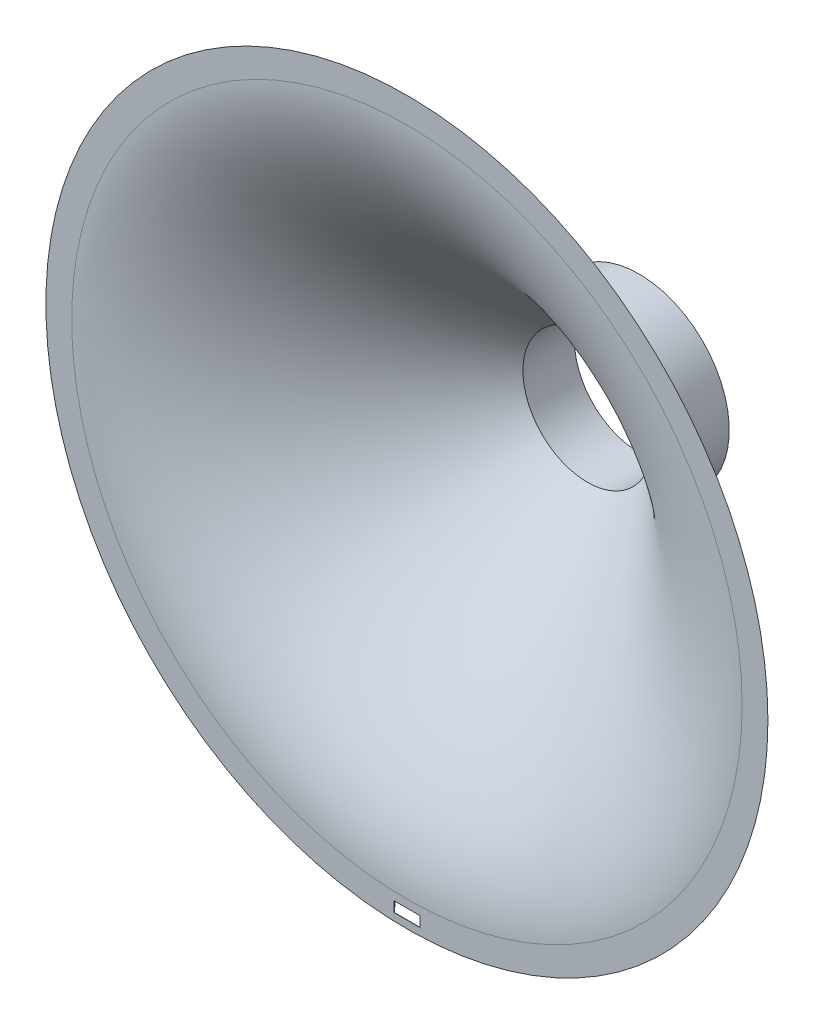
SolidWorks part; units mm, degrees
ref_plane "Front Plane" through (0, 0, 0) normal (0, 0, 1) x (1, 0, 0)
ref_plane "Top Plane" through (0, 0, 0) normal (0, 1, 0) x (1, 0, 0)
ref_plane "Right Plane" through (0, 0, 0) normal (1, 0, 0) x (0, 0, -1)
sketch "Sketch1" plane through (0, 0, 0) normal (1, 0, 0) x (0, 0, -1)
  line L0 (0, 65) -> (0, 47.5) construction
  line L1 (0, 47.5) -> (22.6256, 24.8744) construction
  line L2 (22.6256, 24.8744) -> (35, 12.5) construction
  line L3 (0, 0) -> (0, 16.4687) construction
  line L4 (0, 70) -> (0, 52.5) construction
  line L5 (0, 52.5) -> (22.6256, 29.8744) construction
  line L6 (22.6256, 29.8744) -> (35, 17.5) construction
  line L7 (0, 65) -> (0, 70)
  line L8 (35, 17.5) -> (35, 12.5)
  line L9 (0, 0) -> (22.8545, 0) construction
  spline S0 degree 3 poles (0, 65) (0, 47.5) (22.6256, 24.8744) (35, 12.5) knots 0 0 0 0 1 1 1 1
  spline S1 degree 3 poles (0, 70) (0, 52.5) (22.6256, 29.8744) (35, 17.5) knots 0 0 0 0 1 1 1 1
  dimension "D1" = 52.5
  dimension "D2" = 35
  dimension "D3" = 65
  dimension "D4" = 5
  dimension "D5" = 135
revolve "Revolve1" add sketch "Sketch1" angle 360 about L9
sketch "Sketch2" plane through (0, 0, 0) normal (0, 0, 1) x (1, 0, 0)
  line L4 (0, -65) -> (0, -70) construction
  line L5 (-2.5, -68.5) -> (2.5, -68.5)
  line L6 (-2.5, -68.5) -> (-2.5, -66.5)
  line L7 (-2.5, -66.5) -> (2.5, -66.5)
  line L8 (2.5, -68.5) -> (2.5, -66.5)
  line L9 (-2.5, -68.5) -> (2.5, -66.5) construction
  line L10 (-2.5, -66.5) -> (2.5, -68.5) construction
  circle A1 centre (0, 0) radius 65 construction
  circle A2 centre (0, 0) radius 70 construction
  point P0 (0, -67.5)
  point P13 (0, -67.5)
  dimension "D1" = 2
  dimension "D2" = 5
extrude "Cut-Extrude3" cut sketch "Sketch2" against normal blind 10
sketch "Sketch3" plane through (0, 0, -35) normal (0, 0, -1) x (-1, 0, 0)
  circle A0 centre (0, 0) radius 17.5
  circle A1 centre (0, 0) radius 12.5
  circle A2 centre (0, 0) radius 12.5 construction
  circle A3 centre (0, 0) radius 17.5 construction
extrude "Boss-Extrude1" add sketch "Sketch3" along normal blind 10
